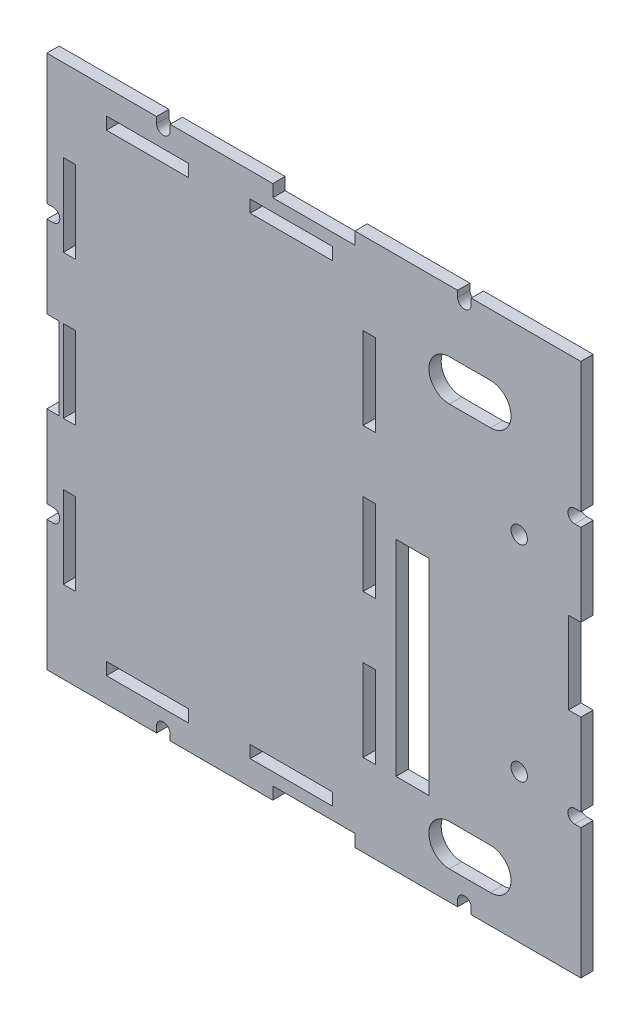
SolidWorks part; units mm, degrees
ref_plane "Front Plane" through (0, 0, 0) normal (0, 0, 1) x (1, 0, 0)
ref_plane "Top Plane" through (0, 0, 0) normal (0, 1, 0) x (1, 0, 0)
ref_plane "Right Plane" through (0, 0, 0) normal (1, 0, 0) x (0, 0, -1)
sketch "Sketch1" plane through (0, 0, 0) normal (0, 0, 1) x (1, 0, 0)
  line L0 (55, 0) -> (-55, 0) construction
  line L1 (65, -65) -> (-65, -65)
  line L2 (65, -65) -> (65, 65)
  line L3 (65, 65) -> (-65, 65)
  line L4 (-65, -65) -> (-65, 65)
  line L5 (65, -65) -> (-65, 65) construction
  line L6 (65, 65) -> (-65, -65) construction
  line L7 (10, 62) -> (-10, 62)
  line L8 (10, 62) -> (10, 65)
  line L9 (10, 65) -> (-10, 65)
  line L10 (-10, 62) -> (-10, 65)
  line L11 (10, 62) -> (-10, 65) construction
  line L12 (10, 65) -> (-10, 62) construction
  line L13 (-62, -10) -> (-65, -10)
  line L14 (-62, -10) -> (-62, 10)
  line L15 (-62, 10) -> (-65, 10)
  line L16 (-65, -10) -> (-65, 10)
  line L17 (-62, -10) -> (-65, 10) construction
  line L18 (-62, 10) -> (-65, -10) construction
  line L19 (10, -65) -> (-10, -65)
  line L20 (-10, -62) -> (-10, -65)
  line L21 (10, -62) -> (-10, -62)
  line L22 (10, -62) -> (10, -65)
  line L23 (0, -55) -> (0, 55) construction
  line L24 (62, 10) -> (65, 10)
  line L25 (65, -10) -> (65, 10)
  line L26 (62, -10) -> (65, -10)
  line L27 (62, -10) -> (62, 10)
  line L28 (-36.65, 63.5) -> (-36.65, 66.5) construction
  line L29 (-38.3, 63.5) -> (-38.3, 66.5)
  line L30 (-35, 63.5) -> (-35, 66.5)
  line L31 (-63.5, 31.65) -> (-66.5, 31.65) construction
  line L32 (-63.5, 30) -> (-66.5, 30)
  line L33 (-63.5, 33.3) -> (-66.5, 33.3)
  line L34 (36.65, 63.5) -> (36.65, 66.5) construction
  line L35 (38.3, 63.5) -> (38.3, 66.5)
  line L36 (35, 63.5) -> (35, 66.5)
  line L37 (63.5, 31.65) -> (66.5, 31.65) construction
  line L38 (63.5, 30) -> (66.5, 30)
  line L39 (63.5, 33.3) -> (66.5, 33.3)
  line L40 (63.5, -31.65) -> (66.5, -31.65) construction
  line L41 (63.5, -30) -> (66.5, -30)
  line L42 (63.5, -33.3) -> (66.5, -33.3)
  line L43 (36.65, -63.5) -> (36.65, -66.5) construction
  line L44 (38.3, -63.5) -> (38.3, -66.5)
  line L45 (35, -63.5) -> (35, -66.5)
  line L46 (-36.65, -63.5) -> (-36.65, -66.5) construction
  line L47 (-38.3, -63.5) -> (-38.3, -66.5)
  line L48 (-35, -63.5) -> (-35, -66.5)
  line L49 (-63.5, -31.65) -> (-66.5, -31.65) construction
  line L50 (-63.5, -30) -> (-66.5, -30)
  line L51 (-63.5, -33.3) -> (-66.5, -33.3)
  line L52 (-58, -45) -> (-61, -45)
  line L53 (-58, -10) -> (-61, -10)
  line L54 (-58, -10) -> (-58, 10)
  line L55 (-58, 10) -> (-61, 10)
  line L56 (-61, -10) -> (-61, 10)
  line L57 (-58, -10) -> (-61, 10) construction
  line L58 (-58, 10) -> (-61, -10) construction
  line L59 (-58, 25) -> (-61, 25)
  line L60 (-58, 25) -> (-58, 45)
  line L61 (-58, 45) -> (-61, 45)
  line L62 (-61, 25) -> (-61, 45)
  line L63 (-58, 25) -> (-61, 45) construction
  line L64 (-58, 45) -> (-61, 25) construction
  line L65 (-61, -25) -> (-61, -45)
  line L66 (-58, -25) -> (-61, -25)
  line L67 (-58, -25) -> (-58, -45)
  line L68 (-15.5, -59) -> (4.5, -59)
  line L69 (-30.5, 56) -> (-50.5, 56)
  line L70 (-30.5, 56) -> (-30.5, 59)
  line L71 (-30.5, 59) -> (-50.5, 59)
  line L72 (-50.5, 56) -> (-50.5, 59)
  line L73 (-30.5, 56) -> (-50.5, 59) construction
  line L74 (-30.5, 59) -> (-50.5, 56) construction
  line L75 (-15.5, 56) -> (4.5, 56)
  line L76 (-15.5, 56) -> (-15.5, 59)
  line L77 (-15.5, 59) -> (4.5, 59)
  line L78 (4.5, 56) -> (4.5, 59)
  line L79 (-15.5, 56) -> (4.5, 59) construction
  line L80 (-15.5, 59) -> (4.5, 56) construction
  line L81 (4.5, -56) -> (4.5, -59)
  line L82 (-15.5, -56) -> (4.5, -56)
  line L83 (-15.5, -56) -> (-15.5, -59)
  line L84 (-30.5, -59) -> (-50.5, -59)
  line L85 (-50.5, -56) -> (-50.5, -59)
  line L86 (-30.5, -56) -> (-50.5, -56)
  line L87 (-30.5, -56) -> (-30.5, -59)
  line L88 (43, -53) -> (33, -53) construction
  line L89 (12, 45) -> (15, 45)
  line L90 (12, 45) -> (12, 25)
  line L91 (12, 25) -> (15, 25)
  line L92 (15, 45) -> (15, 25)
  line L93 (12, 45) -> (15, 25) construction
  line L94 (12, 25) -> (15, 45) construction
  line L95 (15, -10) -> (12, -10)
  line L96 (15, -10) -> (15, 10)
  line L97 (15, 10) -> (12, 10)
  line L98 (12, -10) -> (12, 10)
  line L99 (15, -10) -> (12, 10) construction
  line L100 (15, 10) -> (12, -10) construction
  line L101 (12, -45) -> (15, -45)
  line L102 (12, -45) -> (12, -25)
  line L103 (12, -25) -> (15, -25)
  line L104 (15, -45) -> (15, -25)
  line L105 (12, -45) -> (15, -25) construction
  line L106 (12, -25) -> (15, -45) construction
  line L107 (28, -45) -> (20, -45)
  line L108 (28, -45) -> (28, 5)
  line L109 (28, 5) -> (20, 5)
  line L110 (20, -45) -> (20, 5)
  line L111 (28, -45) -> (20, 5) construction
  line L112 (28, 5) -> (20, -45) construction
  line L117 (43, 45) -> (33, 45) construction
  line L118 (43, 40) -> (33, 40)
  line L119 (43, 50) -> (33, 50)
  line L120 (43, -48) -> (33, -48)
  line L121 (43, -58) -> (33, -58)
  arc A0 (-38.3, 63.5) -> (-35, 63.5) centre (-36.65, 63.5) ccw
  arc A1 (-35, 66.5) -> (-38.3, 66.5) centre (-36.65, 66.5) ccw
  arc A2 (-63.5, 30) -> (-63.5, 33.3) centre (-63.5, 31.65) ccw
  arc A3 (-66.5, 33.3) -> (-66.5, 30) centre (-66.5, 31.65) ccw
  arc A4 (38.3, 63.5) -> (35, 63.5) centre (36.65, 63.5) cw
  arc A5 (35, 66.5) -> (38.3, 66.5) centre (36.65, 66.5) cw
  arc A6 (63.5, 30) -> (63.5, 33.3) centre (63.5, 31.65) cw
  arc A7 (66.5, 33.3) -> (66.5, 30) centre (66.5, 31.65) cw
  arc A8 (63.5, -30) -> (63.5, -33.3) centre (63.5, -31.65) ccw
  arc A9 (66.5, -33.3) -> (66.5, -30) centre (66.5, -31.65) ccw
  arc A10 (38.3, -63.5) -> (35, -63.5) centre (36.65, -63.5) ccw
  arc A11 (35, -66.5) -> (38.3, -66.5) centre (36.65, -66.5) ccw
  arc A12 (-38.3, -63.5) -> (-35, -63.5) centre (-36.65, -63.5) cw
  arc A13 (-35, -66.5) -> (-38.3, -66.5) centre (-36.65, -66.5) cw
  arc A14 (-63.5, -30) -> (-63.5, -33.3) centre (-63.5, -31.65) cw
  arc A15 (-66.5, -33.3) -> (-66.5, -30) centre (-66.5, -31.65) cw
  arc A20 (43, 40) -> (43, 50) centre (43, 45) ccw
  arc A21 (33, 50) -> (33, 40) centre (33, 45) ccw
  circle A22 centre (50, 21) radius 2
  circle A23 centre (50, -29) radius 2
  arc A24 (43, -48) -> (43, -58) centre (43, -53) cw
  arc A25 (33, -58) -> (33, -48) centre (33, -53) cw
  point P0 (0, 0)
  point P6 (0, 63.5)
  point P11 (-63.5, 0)
  point P16 (-36.65, 65)
  point P35 (-65, 31.65)
  point P42 (-59.5, 35)
  point P45 (36.65, 65)
  point P52 (65, 31.65)
  point P59 (65, -31.65)
  point P66 (36.65, -65)
  point P73 (-36.65, -65)
  point P80 (-65, -31.65)
  point P85 (-59.5, 0)
  point P94 (-5.5, 57.5)
  point P100 (-40.5, 57.5)
  point P108 (13.5, -35)
  point P117 (13.5, 35)
  point P123 (13.5, 0)
  point P132 (24, -20)
  point P138 (38, -53)
  point P143 (38, 45)
  point P154 (0, 0)
  point P155 (0, 0)
  dimension "D7" = 1.65
  dimension "D10" = 1.65
  dimension "D29" = 10
  dimension "D31" = 5
  dimension "D35" = 4
  dimension "D1" = 130
  dimension "D2" = 130
  dimension "D3" = 20
  dimension "D4" = 3
  dimension "D5" = 20
  dimension "D6" = 3
  dimension "D8" = 3
  dimension "D9" = 25
  dimension "D11" = 3
  dimension "D12" = 20
  dimension "D13" = 20
  dimension "D14" = 3
  dimension "D15" = 15
  dimension "D16" = 4
  dimension "D17" = 20
  dimension "D18" = 3
  dimension "D19" = 6
  dimension "D20" = 15
  dimension "D21" = 10.5
  dimension "D22" = 10.5
  dimension "D23" = 3
  dimension "D24" = 20
  dimension "D25" = 15
  dimension "D26" = 15
  dimension "D27" = 50
  dimension "D28" = 8
  dimension "5" = 20
  dimension "D30" = 37
  dimension "D32" = 15
  dimension "D33" = 27
  dimension "D34" = 12
  dimension "D36" = 21
  dimension "D37" = 50
  dimension "D38" = 50
extrude "Boss-Extrude1" add sketch "Sketch1" along normal blind 3 contours L26 L27 L24 L2 L3 L8 L7 L10 L4 L15 L14 L13 L1 L20 L21 L22 region at (-0.6989, 0.6267, 0)
